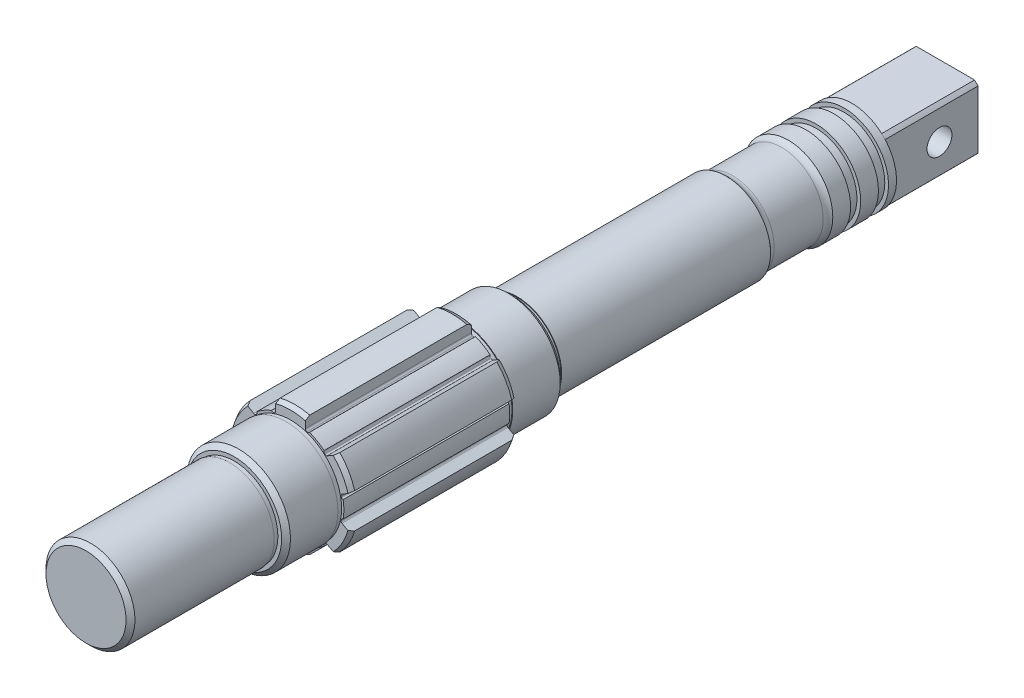
SolidWorks part; units mm, degrees
ref_plane "前视基准面" through (0, 0, 0) normal (0, 0, 1) x (1, 0, 0)
ref_plane "上视基准面" through (0, 0, 0) normal (0, 1, 0) x (1, 0, 0)
ref_plane "右视基准面" through (0, 0, 0) normal (1, 0, 0) x (0, 0, -1)
other "Configuration Table"
sketch "草图1" plane through (0, 0, 0) normal (0, 0, 1) x (1, 0, 0)
  line L1 (9.8266, -11) -> (-9.8266, -11)
  line L2 (11, -9.8266) -> (11, 9.8266)
  line L3 (9.8266, 11) -> (-9.8266, 11)
  line L4 (-11, -9.8266) -> (-11, 9.8266)
  arc A0 (-9.8266, 11) -> (-11, 9.8266) centre (0, 0) ccw
  arc A1 (9.8266, -11) -> (11, -9.8266) centre (0, 0) ccw
  arc A2 (-11, -9.8266) -> (-9.8266, -11) centre (0, 0) ccw
  arc A3 (11, 9.8266) -> (9.8266, 11) centre (0, 0) ccw
  point P5 (-11, 1.7924)
  dimension "D1" = 29.5
  dimension "D2" = 11
  dimension "D3" = 11
  dimension "D4" = 11
  dimension "D5" = 11
extrude "凸台-拉伸1" add sketch "草图1" along normal blind 31.5
sketch "草图2" plane through (11, 0, 0) normal (1, 0, 0) x (0, 0, -1)
  circle A0 centre (-13, 0) radius 4.2
  dimension "D2" = 8.4
extrude "切除-拉伸1" cut sketch "草图2" against normal blind 31.5
sketch "草图3" plane through (0, 0, 31.5) normal (0, 0, 1) x (1, 0, 0)
  circle A0 centre (0, 0) radius 15
  dimension "D1" = 30
extrude "凸台-拉伸2" add sketch "草图3" along normal blind 2.7
sketch "草图4" plane through (0, 0, 34.2) normal (0, 0, 1) x (1, 0, 0)
  circle A0 centre (0, 0) radius 13.75
  dimension "D1" = 27.5
extrude "凸台-拉伸3" add sketch "草图4" along normal blind 3.4
sketch "草图5" plane through (0, 0, 37.6) normal (0, 0, 1) x (1, 0, 0)
  circle A0 centre (0, 0) radius 15
extrude "凸台-拉伸4" add sketch "草图5" along normal blind 6
sketch "草图6" plane through (0, 0, 43.6) normal (0, 0, 1) x (1, 0, 0)
  circle A0 centre (0, 0) radius 13.75
  dimension "D1" = 27.5
extrude "凸台-拉伸5" add sketch "草图6" along normal blind 3.4
sketch "草图7" plane through (0, 0, 47) normal (0, 0, 1) x (1, 0, 0)
  circle A0 centre (0, 0) radius 15
extrude "凸台-拉伸6" add sketch "草图7" along normal blind 6
sketch "草图8" plane through (0, 0, 53) normal (0, 0, 1) x (1, 0, 0)
  circle A0 centre (0, 0) radius 14
extrude "凸台-拉伸7" add sketch "草图8" along normal blind 21
sketch "草图9" plane through (0, 0, 74) normal (0, 0, 1) x (1, 0, 0)
  circle A0 centre (0, 0) radius 15
extrude "凸台-拉伸8" add sketch "草图9" along normal blind 70.5
fillet "圆角1" radius 3 1 edges at (14, 0, 74)
fillet "圆角2" radius 3 1 edges at (14, 0, 53)
sketch "草图10" plane through (0, 0, 144.5) normal (0, 0, 1) x (1, 0, 0)
  circle A0 centre (0, 0) radius 14.75
  dimension "D1" = 29.5
extrude "凸台-拉伸9" add sketch "草图10" along normal blind 1.5
sketch "草图11" plane through (0, 0, 146) normal (0, 0, 1) x (1, 0, 0)
  circle A0 centre (0, 0) radius 17.5
extrude "凸台-拉伸10" add sketch "草图11" along normal blind 17.5
chamfer "倒角1" distance 1.5 angle 45 1 edges at (17.5, 0, 146)
sketch "草图12" plane through (0, 0, 163.5) normal (0, 0, 1) x (1, 0, 0)
  circle A0 centre (0, 0) radius 17.25
  dimension "D1" = 34.5
extrude "凸台-拉伸11" add sketch "草图12" along normal blind 1.5
sketch "草图13" plane through (0, 0, 165) normal (0, 0, 1) x (1, 0, 0)
  circle A0 centre (0, 0) radius 21
extrude "凸台-拉伸12" add sketch "草图13" along normal blind 56
chamfer "倒角2" distance 1.5 angle 30 1 edges at (21, 0, 221) first distance on face at (21, 0, 221)
chamfer "倒角4" distance 1.5 angle 30 1 edges at (21, 0, 165) first distance on face at (21, 0, 219.5)
sketch "草图15" plane through (0, 0, 221) normal (0, 0, 1) x (1, 0, 0)
  line L0 (11.3474, 13.9542) -> (11.3546, 13.9668)
  line L1 (12.3918, 12.9279) -> (15.1635, 14.5282)
  line L2 (5, 17.1956) -> (5, 20.3961)
  line L3 (6.411, 16.8042) -> (6.4183, 16.8168)
  line L6 (17.7584, -2.85) -> (17.7729, -2.85)
  line L7 (17.3918, -4.2677) -> (20.1635, -5.8679)
  line L10 (17.3918, 4.2677) -> (20.1635, 5.8679)
  line L11 (17.7584, 2.85) -> (17.7729, 2.85)
  line L12 (6.411, -16.8042) -> (6.4183, -16.8168)
  line L13 (-6.411, 16.8042) -> (-6.4183, 16.8168)
  line L14 (-5, 17.1956) -> (-5, 20.3961)
  line L15 (-12.3918, 12.9279) -> (-15.1635, 14.5282)
  line L16 (-11.3474, 13.9542) -> (-11.3546, 13.9668)
  line L18 (5, -17.1956) -> (5, -20.3961)
  line L19 (12.3918, -12.9279) -> (15.1635, -14.5282)
  line L20 (11.3474, -13.9542) -> (11.3546, -13.9668)
  line L21 (-11.3474, -13.9542) -> (-11.3546, -13.9668)
  line L22 (-12.3918, -12.9279) -> (-15.1635, -14.5282)
  line L23 (-5, -17.1956) -> (-5, -20.3961)
  line L24 (-6.411, -16.8042) -> (-6.4183, -16.8168)
  line L25 (-17.7584, 2.85) -> (-17.7729, 2.85)
  line L26 (-17.3918, 4.2677) -> (-20.1635, 5.8679)
  line L27 (-17.3918, -4.2677) -> (-20.1635, -5.8679)
  line L28 (-17.7584, -2.85) -> (-17.7729, -2.85)
  arc A0 (-5, 20.3961) -> (-15.1635, 14.5282) centre (0, 0) ccw
  arc A1 (-6.4183, 16.8168) -> (-11.3546, 13.9668) centre (0, 0) ccw
  arc A2 (-11.4826, 13.1398) -> (-11.6335, 13.0063) centre (0, 0) ccw
  arc A5 (-5.4471, 16.578) -> (-5.6381, 16.5141) centre (0, 0) ccw
  arc A6 (-11.3474, 13.9542) -> (-11.4826, 13.1398) centre (-11.9103, 13.6292) cw
  arc A7 (-11.6335, 13.0063) -> (-12.3918, 12.9279) centre (-12.0668, 13.4908) cw
  arc A8 (-5, 17.1956) -> (-5.4471, 16.578) centre (-5.65, 17.1956) cw
  arc A9 (-5.6381, 16.5141) -> (-6.411, 16.8042) centre (-5.8481, 17.1292) cw
  arc A14 (15.1635, 14.5282) -> (5, 20.3961) centre (0, 0) ccw
  arc A15 (11.3546, 13.9668) -> (6.4183, 16.8168) centre (0, 0) ccw
  arc A16 (5.6381, 16.5141) -> (5.4471, 16.578) centre (0, 0) ccw
  arc A17 (11.6335, 13.0063) -> (11.4826, 13.1398) centre (0, 0) ccw
  arc A18 (6.411, 16.8042) -> (5.6381, 16.5141) centre (5.8481, 17.1292) cw
  arc A19 (5.4471, 16.578) -> (5, 17.1956) centre (5.65, 17.1956) cw
  arc A20 (12.3918, 12.9279) -> (11.6335, 13.0063) centre (12.0668, 13.4908) cw
  arc A21 (11.4826, 13.1398) -> (11.3474, 13.9542) centre (11.9103, 13.6292) cw
  arc A23 (20.1635, -5.8679) -> (20.1635, 5.8679) centre (0, 0) ccw
  arc A24 (17.7729, -2.85) -> (17.7729, 2.85) centre (0, 0) ccw
  arc A25 (17.1206, 3.3743) -> (17.0806, 3.5717) centre (0, 0) ccw
  arc A26 (17.0806, -3.5717) -> (17.1206, -3.3743) centre (0, 0) ccw
  arc A27 (17.7584, 2.85) -> (17.1206, 3.3743) centre (17.7584, 3.5) cw
  arc A28 (17.0806, 3.5717) -> (17.3918, 4.2677) centre (17.7168, 3.7047) cw
  arc A29 (17.3918, -4.2677) -> (17.0806, -3.5717) centre (17.7168, -3.7047) cw
  arc A30 (17.1206, -3.3743) -> (17.7584, -2.85) centre (17.7584, -3.5) cw
  arc A32 (5, -20.3961) -> (15.1635, -14.5282) centre (0, 0) ccw
  arc A33 (6.4183, -16.8168) -> (11.3546, -13.9668) centre (0, 0) ccw
  arc A34 (11.4826, -13.1398) -> (11.6335, -13.0063) centre (0, 0) ccw
  arc A35 (5.4471, -16.578) -> (5.6381, -16.5141) centre (0, 0) ccw
  arc A36 (11.3474, -13.9542) -> (11.4826, -13.1398) centre (11.9103, -13.6292) cw
  arc A37 (11.6335, -13.0063) -> (12.3918, -12.9279) centre (12.0668, -13.4908) cw
  arc A38 (5, -17.1956) -> (5.4471, -16.578) centre (5.65, -17.1956) cw
  arc A39 (5.6381, -16.5141) -> (6.411, -16.8042) centre (5.8481, -17.1292) cw
  arc A41 (-15.1635, -14.5282) -> (-5, -20.3961) centre (0, 0) ccw
  arc A42 (-11.3546, -13.9668) -> (-6.4183, -16.8168) centre (0, 0) ccw
  arc A43 (-5.6381, -16.5141) -> (-5.4471, -16.578) centre (0, 0) ccw
  arc A44 (-11.6335, -13.0063) -> (-11.4826, -13.1398) centre (0, 0) ccw
  arc A45 (-6.411, -16.8042) -> (-5.6381, -16.5141) centre (-5.8481, -17.1292) cw
  arc A46 (-5.4471, -16.578) -> (-5, -17.1956) centre (-5.65, -17.1956) cw
  arc A47 (-12.3918, -12.9279) -> (-11.6335, -13.0063) centre (-12.0668, -13.4908) cw
  arc A48 (-11.4826, -13.1398) -> (-11.3474, -13.9542) centre (-11.9103, -13.6292) cw
  arc A50 (-20.1635, 5.8679) -> (-20.1635, -5.8679) centre (0, 0) ccw
  arc A51 (-17.7729, 2.85) -> (-17.7729, -2.85) centre (0, 0) ccw
  arc A52 (-17.1206, -3.3743) -> (-17.0806, -3.5717) centre (0, 0) ccw
  arc A53 (-17.0806, 3.5717) -> (-17.1206, 3.3743) centre (0, 0) ccw
  arc A54 (-17.7584, -2.85) -> (-17.1206, -3.3743) centre (-17.7584, -3.5) cw
  arc A55 (-17.0806, -3.5717) -> (-17.3918, -4.2677) centre (-17.7168, -3.7047) cw
  arc A56 (-17.3918, 4.2677) -> (-17.0806, 3.5717) centre (-17.7168, 3.7047) cw
  arc A57 (-17.1206, 3.3743) -> (-17.7584, 2.85) centre (-17.7584, 3.5) cw
  point P10 (-15.6385, 7.4965)
  point P11 (0, 0)
  point P14 (5, 16.7183)
  point P23 (0, 0)
  point P27 (-11.9785, 12.6893)
  point P36 (-11.9785, 12.6893)
  point P39 (-5, 16.7183)
  point P49 (16.9785, 4.029)
  point P66 (11.9785, -12.6893)
  point P83 (-5, -16.7183)
  point P100 (-16.9785, -4.029)
  point P112 (0, 0)
  dimension "D1" = 6
  dimension "D4" = 34.9
  dimension "D5" = 0.65
  dimension "D6" = 0.65
extrude "切除-拉伸2" cut sketch "草图15" against normal blind 56
sketch "草图16" plane through (0, 0, 221) normal (0, 0, 1) x (1, 0, 0)
  circle A0 centre (0, 0) radius 17.25
  dimension "D1" = 34.5
extrude "凸台-拉伸13" add sketch "草图16" along normal blind 1.5
sketch "草图17" plane through (0, 0, 222.5) normal (0, 0, 1) x (1, 0, 0)
  circle A0 centre (0, 0) radius 17.5
extrude "凸台-拉伸14" add sketch "草图17" along normal blind 17.5
chamfer "倒角5" distance 1.5 angle 45 1 edges at (17.5, 0, 240)
sketch "草图18" plane through (0, 0, 240) normal (0, 0, 1) x (1, 0, 0)
  circle A0 centre (0, 0) radius 14.75
  dimension "D1" = 29.5
extrude "凸台-拉伸15" add sketch "草图18" along normal blind 1.5
sketch "草图19" plane through (0, 0, 241.5) normal (0, 0, 1) x (1, 0, 0)
  circle A0 centre (0, 0) radius 15
extrude "凸台-拉伸16" add sketch "草图19" along normal blind 48.5
chamfer "倒角6" distance 1.5 angle 45 1 edges at (15, 0, 290)
